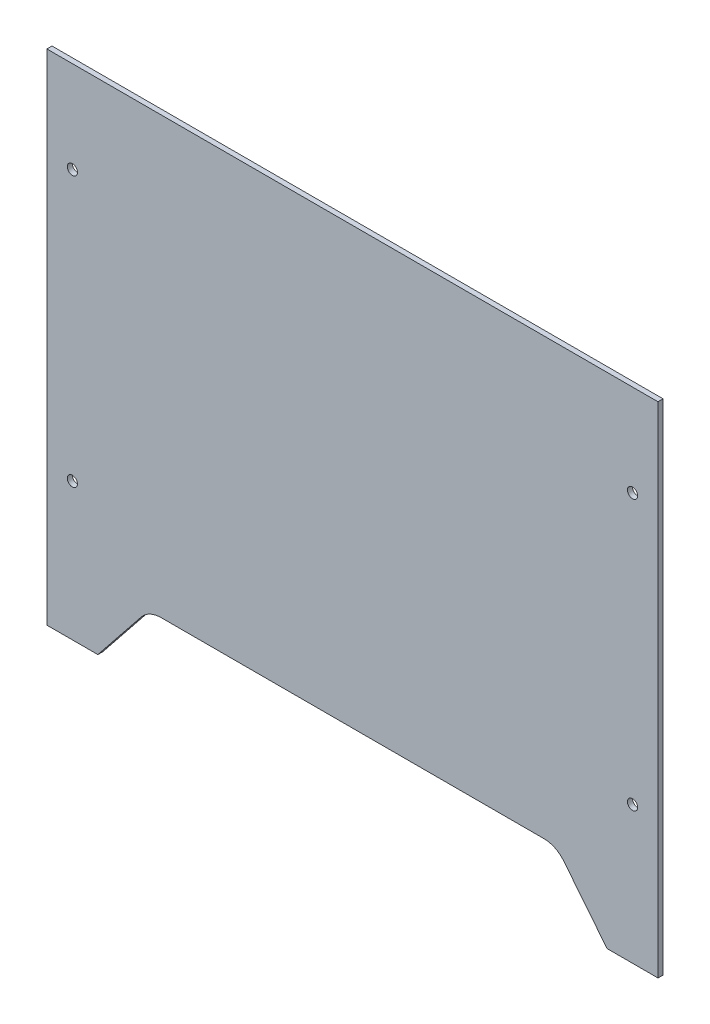
SolidWorks part; units mm, degrees
ref_plane "前视基准面" through (0, 0, 0) normal (0, 0, 1) x (1, 0, 0)
ref_plane "上视基准面" through (0, 0, 0) normal (0, 1, 0) x (1, 0, 0)
ref_plane "右视基准面" through (0, 0, 0) normal (1, 0, 0) x (0, 0, -1)
sketch "Sketch1" plane through (0, 0, 0) normal (0, 0, 1) x (1, 0, 0)
  line L0 (0, -98) -> (0, 0) construction
  line L1 (-120, -98) -> (120, -98) construction
  line L2 (-120, -98) -> (-120, 98)
  line L3 (-120, 98) -> (120, 98)
  line L4 (120, -98) -> (120, 98)
  line L5 (-120, -98) -> (120, 98) construction
  line L6 (-120, 98) -> (120, -98) construction
  line L7 (-75.1938, -73) -> (75.1938, -73)
  line L8 (83.0024, -76.753) -> (100, -98)
  line L9 (100, -98) -> (120, -98)
  line L10 (-100, -98) -> (-120, -98)
  line L11 (-83.0024, -76.753) -> (-100, -98)
  line L12 (110, 98) -> (110, -98) construction
  arc A0 (83.0024, -76.753) -> (75.1938, -73) centre (75.1938, -83) ccw
  arc A1 (-83.0024, -76.753) -> (-75.1938, -73) centre (-75.1938, -83) cw
  circle A2 centre (110, 62) radius 2
  circle A3 centre (110, -44) radius 2
  circle A4 centre (-110, -44) radius 2
  circle A5 centre (-110, 62) radius 2
  point P0 (0, 0)
  point P13 (80, -73)
  point P18 (0, -73)
  dimension "D6" = 10
  dimension "D8" = 4
  dimension "D9" = 4
  dimension "D1" = 240
  dimension "D2" = 196
  dimension "D3" = 25
  dimension "D4" = 20
  dimension "D5" = 80
  dimension "D7" = 10
  dimension "D10" = 36
  dimension "D11" = 106
extrude "Boss-Extrude1" add sketch "Sketch1" along normal blind 2
